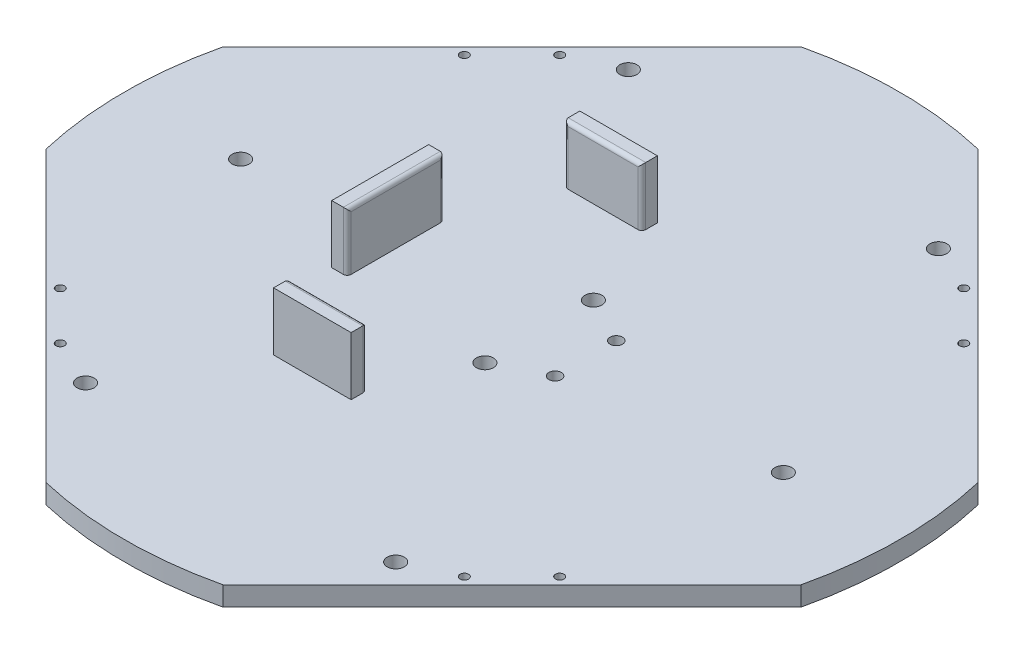
SolidWorks part; units mm, degrees
ref_plane "Front Plane" through (0, 0, 0) normal (0, 0, 1) x (1, 0, 0)
ref_plane "Top Plane" through (0, 0, 0) normal (0, 1, 0) x (1, 0, 0)
ref_plane "Right Plane" through (0, 0, 0) normal (1, 0, 0) x (0, 0, -1)
sketch "Sketch1" plane through (0, 0, 0) normal (0, 1, 0) x (1, 0, 0)
  line L2 (97.3532, -22.8549) -> (22.8549, -97.3532)
  line L3 (97.3532, 22.8549) -> (22.8549, 97.3532)
  line L4 (-22.8549, 97.3532) -> (-97.3532, 22.8549)
  line L5 (-22.8549, -97.3532) -> (-97.3532, -22.8549)
  line L6 (100, 0) -> (-100, 0) construction
  line L7 (0, 100) -> (0, -100) construction
  arc A0 (-22.8549, -97.3532) -> (22.8549, -97.3532) centre (0, 0) ccw
  arc A1 (97.3532, -22.8549) -> (97.3532, 22.8549) centre (0, 0) ccw
  arc A2 (22.8549, 97.3532) -> (-22.8549, 97.3532) centre (0, 0) ccw
  arc A4 (-97.3532, 22.8549) -> (-97.3532, -22.8549) centre (0, 0) ccw
  dimension "D2" = 200
  dimension "D1" = 170
  dimension "D3" = 170
extrude "Boss-Extrude1" add sketch "Sketch1" along normal blind 5
sketch "Sketch2" plane through (0, 5, 0) normal (0, 1, 0) x (1, 0, 0)
  line L0 (3.5, -14) -> (10.5, -14) construction
  line L63 (-40, -70) -> (40, -70) construction
  line L76 (7.9, -10.25) -> (7.9, 10.25) construction
  line L79 (7, -14) -> (7, 15.9726) construction
  circle A24 centre (-40, -70) radius 2.2
  circle A25 centre (40, -70) radius 2.2
  circle A26 centre (40, 70) radius 2.2
  circle A27 centre (-40, 70) radius 2.2
  circle A28 centre (-70, 0) radius 2.2
  circle A29 centre (70, 0) radius 2.2
  circle A30 centre (7, -14) radius 2.2
  circle A31 centre (7, 14) radius 2.2
  point P30 (35.5, -14)
  point P85 (0, 0)
  point P98 (0, 0)
  dimension "D40" = 4.4
  dimension "D41" = 4.4
  dimension "D42" = 4.4
  dimension "D43" = 4.4
  dimension "D46" = 4.4
  dimension "D39" = 80
  dimension "D44" = 140
extrude "Cut-Extrude1" cut sketch "Sketch2" against normal through all
sketch "Sketch3" plane through (0, 5, 0) normal (0, 1, 0) x (1, 0, 0)
  line L0 (-60.1041, 60.1041) -> (60.1041, -60.1041) construction
  line L1 (-22.8549, 97.3532) -> (-97.3532, 22.8549) construction
  line L2 (22.8549, -97.3532) -> (97.3532, -22.8549) construction
  line L3 (-60.1041, -60.1041) -> (60.1041, 60.1041) construction
  line L4 (-97.3532, -22.8549) -> (-22.8549, -97.3532) construction
  line L5 (97.3532, 22.8549) -> (22.8549, 97.3532) construction
  line L6 (-51.1238, 69.0843) -> (-69.0843, 51.1238) construction
  line L7 (-69.0843, 51.1238) -> (-60.9526, 42.9921) construction
  line L8 (-60.9526, 42.9921) -> (-42.9921, 60.9526) construction
  line L9 (-42.9921, 60.9526) -> (-51.1238, 69.0843) construction
  line L10 (-64.4174, 52.1138) -> (-52.1138, 64.4174) construction
  line L11 (-56.2503, 47.6944) -> (-41.0475, 32.4916) construction
  line L12 (-41.0475, 32.4916) -> (-32.4916, 41.0475) construction
  line L13 (-32.4916, 41.0475) -> (-47.6944, 56.2503) construction
  line L14 (-59.0434, 61.1647) -> (-66.1145, 68.2358) construction
  line L15 (-66.1145, 68.2358) -> (-68.2358, 66.1145) construction
  line L16 (-68.2358, 66.1145) -> (-61.1647, 59.0434) construction
  line L17 (60.1041, 60.1041) -> (-60.1041, -60.1041) construction
  line L18 (-60.1041, 60.1041) -> (60.1041, -60.1041) construction
  line L19 (69.0843, 51.1238) -> (51.1238, 69.0843) construction
  line L20 (51.1238, 69.0843) -> (42.9921, 60.9526) construction
  line L21 (42.9921, 60.9526) -> (60.9526, 42.9921) construction
  line L22 (60.9526, 42.9921) -> (69.0843, 51.1238) construction
  line L23 (52.1138, 64.4174) -> (64.4174, 52.1138) construction
  line L24 (47.6944, 56.2503) -> (32.4916, 41.0475) construction
  line L25 (32.4916, 41.0475) -> (41.0475, 32.4916) construction
  line L26 (41.0475, 32.4916) -> (56.2503, 47.6944) construction
  line L27 (61.1647, 59.0434) -> (68.2358, 66.1145) construction
  line L28 (68.2358, 66.1145) -> (66.1145, 68.2358) construction
  line L29 (66.1145, 68.2358) -> (59.0434, 61.1647) construction
  line L30 (60.1041, -60.1041) -> (-60.1041, 60.1041) construction
  line L31 (60.1041, 60.1041) -> (-60.1041, -60.1041) construction
  line L32 (51.1238, -69.0843) -> (69.0843, -51.1238) construction
  line L33 (69.0843, -51.1238) -> (60.9526, -42.9921) construction
  line L34 (60.9526, -42.9921) -> (42.9921, -60.9526) construction
  line L35 (42.9921, -60.9526) -> (51.1238, -69.0843) construction
  line L36 (64.4174, -52.1138) -> (52.1138, -64.4174) construction
  line L37 (56.2503, -47.6944) -> (41.0475, -32.4916) construction
  line L38 (41.0475, -32.4916) -> (32.4916, -41.0475) construction
  line L39 (32.4916, -41.0475) -> (47.6944, -56.2503) construction
  line L40 (59.0434, -61.1647) -> (66.1145, -68.2358) construction
  line L41 (66.1145, -68.2358) -> (68.2358, -66.1145) construction
  line L42 (68.2358, -66.1145) -> (61.1647, -59.0434) construction
  line L43 (-60.1041, -60.1041) -> (60.1041, 60.1041) construction
  line L44 (60.1041, -60.1041) -> (-60.1041, 60.1041) construction
  line L45 (-69.0843, -51.1238) -> (-51.1238, -69.0843) construction
  line L46 (-51.1238, -69.0843) -> (-42.9921, -60.9526) construction
  line L47 (-42.9921, -60.9526) -> (-60.9526, -42.9921) construction
  line L48 (-60.9526, -42.9921) -> (-69.0843, -51.1238) construction
  line L49 (-52.1138, -64.4174) -> (-64.4174, -52.1138) construction
  line L50 (-47.6944, -56.2503) -> (-32.4916, -41.0475) construction
  line L51 (-32.4916, -41.0475) -> (-41.0475, -32.4916) construction
  line L52 (-41.0475, -32.4916) -> (-56.2503, -47.6944) construction
  line L53 (-61.1647, -59.0434) -> (-68.2358, -66.1145) construction
  line L54 (-68.2358, -66.1145) -> (-66.1145, -68.2358) construction
  line L55 (-66.1145, -68.2358) -> (-59.0434, -61.1647) construction
  line L56 (0, 0) -> (-32.4916, 41.0475) construction
  line L57 (0, 0) -> (41.0475, 32.4916) construction
  line L58 (13.4136, 0) -> (21.2136, 0) construction
  line L59 (5.6136, -10.1) -> (21.2136, -10.1) construction
  line L60 (5.6136, -10.1) -> (5.6136, 10.1) construction
  line L61 (5.6136, 10.1) -> (21.2136, 10.1) construction
  line L62 (21.2136, -10.1) -> (21.2136, 10.1) construction
  line L63 (5.6136, -10.1) -> (21.2136, 10.1) construction
  line L64 (5.6136, 10.1) -> (21.2136, -10.1) construction
  line L65 (21.2136, 10.1) -> (17.4036, 10.1) construction
  line L66 (21.2136, 10.1) -> (21.2136, 6.29) construction
  line L67 (21.2136, 6.29) -> (17.4036, 6.29) construction
  line L68 (17.4036, 10.1) -> (17.4036, 6.29) construction
  line L73 (0, 0) -> (-13.5, 0) construction
  line L74 (3, -35.5) -> (-30, -35.5) construction
  line L75 (3, -35.5) -> (3, 35.5) construction
  line L76 (3, 35.5) -> (-30, 35.5) construction
  line L77 (-30, -35.5) -> (-30, 35.5) construction
  line L78 (3, -35.5) -> (-30, 35.5) construction
  line L79 (3, 35.5) -> (-30, -35.5) construction
  line L80 (-22, 35.5) -> (-2, 35.5)
  line L81 (-22, 35.5) -> (-22, 39.5)
  line L82 (-22, 39.5) -> (-2, 39.5)
  line L83 (-2, 35.5) -> (-2, 39.5)
  line L84 (-30, 12.5) -> (-34, 12.5)
  line L85 (-30, 12.5) -> (-30, -12.5)
  line L86 (-30, -12.5) -> (-34, -12.5)
  line L87 (-34, 12.5) -> (-34, -12.5)
  line L88 (-2, -35.5) -> (-2, -39.5)
  line L89 (-22, -39.5) -> (-2, -39.5)
  line L90 (-22, -35.5) -> (-22, -39.5)
  line L91 (-22, -35.5) -> (-2, -35.5)
  circle A0 centre (-52.1138, 64.4174) radius 1.1
  circle A1 centre (-64.4174, 52.1138) radius 1.1
  circle A2 centre (64.4174, 52.1138) radius 1.1
  circle A3 centre (52.1138, 64.4174) radius 1.1
  circle A4 centre (52.1138, -64.4174) radius 1.1
  circle A5 centre (64.4174, -52.1138) radius 1.1
  circle A6 centre (-64.4174, -52.1138) radius 1.1
  circle A7 centre (-52.1138, -64.4174) radius 1.1
  circle A8 centre (19.0036, 7.89) radius 1.6
  circle A9 centre (19.0036, -7.89) radius 1.6
  circle A11 centre (7, 14) radius 2.2 construction
  point P15 (-60.1041, 60.1041)
  point P21 (-58.2656, 58.2656)
  point P26 (-36.7696, 36.7696)
  point P33 (-67.1751, 67.1751)
  point P35 (-131.0133, 45.9953)
  point P111 (-13.5, 0)
  point P122 (5.6136, 0)
  point P126 (-30, 0)
  point P127 (-2, 37.5)
  dimension "D2" = 2.2
  dimension "D3" = 2.2
  dimension "D14" = 20.2
  dimension "D16" = 3.2
  dimension "D1" = 25.4
  dimension "D4" = 17.4
  dimension "D5" = 2.6
  dimension "D6" = 11.5
  dimension "D7" = 12.1
  dimension "D8" = 21.5
  dimension "D9" = 10
  dimension "D10" = 3
  dimension "D11" = 4
  dimension "D12" = 90
  dimension "D13" = 52.3508
  dimension "D15" = 15.6
  dimension "D17" = 4
  dimension "D18" = 71
  dimension "D19" = 33
  dimension "D20" = 5.6136
  dimension "D21" = 3.81
  dimension "D22" = 4
  dimension "D23" = 25
  dimension "D24" = 4
  dimension "D25" = 20
  dimension "D26" = 5
sketch "Sketch4" plane through (0, 5, 0) normal (0, 1, 0) x (1, 0, 0)
extrude "Cut-Extrude3" cut sketch "Sketch3" against normal through all contours A7 | A6 | A5 | A4 | A2 | A3 | A0 | A1 | A9 | A8 region at (-52.1138, 5, -64.4174) region at (-64.4174, 5, -52.1138) region at (64.4174, 5, -52.1138) region at (52.1138, 5, -64.4174) region at (52.1138, 5, 64.4174) region at (64.4174, 5, 52.1138) region at (-64.4174, 5, 52.1138) region at (-52.1138, 5, 64.4174) region at (19.0036, 5, 7.89)
extrude "Boss-Extrude2" add sketch "Sketch3<3>" along normal blind 15 contours L91 L90 L89 L88 | L84 L87 L86 L85 | L80 L83 L82 L81 region at (-12, 5, -37.5) region at (-32, 5, 0) region at (-12, 5, 37.5)
sketch "Sketch3<3>" plane through (0, 5, 0) normal (0, 1, 0) x (1, 0, 0) same geometry as "Sketch3"
fillet "Fillet1" radius 1 9 edges at (-22, 12.5, 35.5) (-2, 12.5, -35.5) (-12, 20, -35.5) (-22, 12.5, -35.5) (-2, 12.5, 35.5) (-30, 12.5, 12.5) (-30, 12.5, -12.5) (-12, 20, 35.5) (-30, 20, 0)
